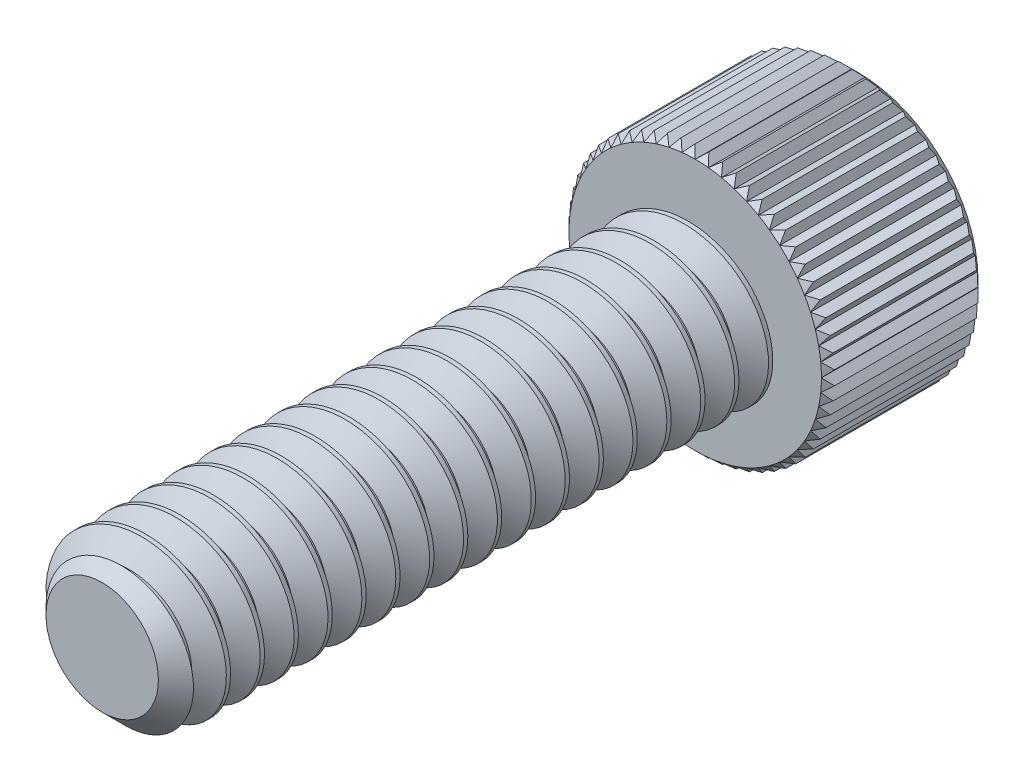
SolidWorks part; units mm, degrees
note: '?' marks a value the reader was unsure of.
ref_plane "Front Plane" through (0, 0, 0) normal (0, 0, 1) x (1, 0, 0)
ref_plane "Top Plane" through (0, 0, 0) normal (0, 1, 0) x (1, 0, 0)
ref_plane "Right Plane" through (0, 0, 0) normal (1, 0, 0) x (0, 0, -1)
sketch "Sketch0" plane through (0, 0, 0) normal (1, 0, 0) x (0, 0, -1)
  line L0 (0, 0) -> (7.9375, 0) construction
  point P2 (10.1219, 0)
  point P4 (0, 0)
  dimension "D1" = 7.9375
  dimension "D2" = 2.1844
  dimension "Min Thread" = 0
sketch "Sketch1" plane through (0, 0, 0) normal (0, 0, 1) x (1, 0, 0)
  circle A0 centre (0, 0) radius 1.0922
  dimension "OD" = 2.1844
extrude "Extrude1" add sketch "Sketch1" against normal blind 7.9375
sketch "Sketch2" plane through (0, 0, 0) normal (0, 0, 1) x (1, 0, 0)
  circle A0 centre (0, 0) radius 1.0922 construction
  circle A1 centre (0, 0) radius 1.0922
curve "Helix/Spiral1" pitch 0.4536 height 8.3911 radius 1.0922 centre (0, 0, 0) axis (0, 0, -1) start towards (0, 1, 0) parameters "pitch"=0.4536
chamfer "Chamfer3" distance 0.3402 angle 45 1 edges at (1.0922, 0, 0)
sketch "Sketch3" plane through (0, 0, 0) normal (1, 0, 0) x (0, 0, -1)
  line L0 (-0.3969, 1.0922) -> (-0.2268, 0.7976)
  line L1 (-0.2268, 0.7976) -> (-0.1701, 0.7976)
  line L2 (-0.1701, 0.7976) -> (0, 1.0922)
  line L3 (-0.3969, 1.0922) -> (0, 1.0922)
  line L4 (-0.1984, 1.0922) -> (-0.1984, 0.7976) construction
  line L5 (-0.3118, 0.9449) -> (-0.085, 0.9449) construction
  line L6 (0, 1.0922) -> (0, -1.0922) construction
  dimension "D1" = 0.0567
  dimension "D2" = 0.2268
  dimension "D3" = 60
sweep "Cut-Sweep1" cut profiles "Sketch3" path "Helix/Spiral1" align with end faces yes
sketch "Sketch5" plane through (0, 0, 0) normal (1, 0, 0) x (0, 0, -1)
  line L0 (7.9375, -0.7793) -> (7.9375, 0.8061) construction
  line L1 (7.9375, 1.0922) -> (0, 1.0922)
  line L2 (7.9375, 1.0922) -> (7.9375, 0)
  line L3 (7.9375, 0) -> (-0.3975, 0)
  line L4 (0, 0) -> (7.9375, 0) construction
  line L5 (0, 1.0922) -> (-0.3975, 0)
  line L6 (0, 0) -> (10.4775, 0) construction
  dimension "D1" = 70
  dimension "D3" = 2.54
revolve "partially thread" [suppressed] add sketch "Sketch5" angle 360 about L6
sketch "Sketch6" plane through (0, 0, -7.9375) normal (0, 0, -1) x (-1, 0, 0)
  circle A0 centre (0, 0) radius 1.778
  dimension "head dia" = 3.556
extrude "Extrude2" add sketch "Sketch6" along normal blind 2.1844
sketch "Sketch7" plane through (0, 0, -10.1219) normal (0, 0, -1) x (-1, 0, 0)
  line L1 (0, 1.1457) -> (-0.9922, 0.5728)
  line L2 (-0.9922, 0.5728) -> (-0.9922, -0.5728)
  line L3 (-0.9922, -0.5728) -> (0, -1.1457)
  line L4 (0, -1.1457) -> (0.9922, -0.5728)
  line L5 (0.9922, -0.5728) -> (0.9922, 0.5728)
  line L6 (0.9922, 0.5728) -> (0, 1.1457)
  circle A0 centre (0, 0) radius 0.9922 construction
  dimension "hex dia" = 1.9844
extrude "Cut-Extrude1" cut sketch "Sketch7" against normal blind 1.4883
sketch "Sketch8" plane through (0, 0, -10.1219) normal (0, 0, -1) x (-1, 0, 0)
  circle A0 centre (0, 0) radius 1.1457
extrude "Cut-Extrude2" cut sketch "Sketch8" against normal through all draft 45
chamfer "Chamfer1" distance 0.1778 angle 45 1 edges at (-1.778, 0, -10.1219)
chamfer "Chamfer2" distance 0.0889 angle 45 1 edges at (-1.778, 0, -7.9375)
sketch "Sketch9" plane through (0, 0, 0) normal (1, 0, 0) x (0, 0, -1)
  line L0 (0, 1.0922) -> (0, -1.0922) construction
  line L1 (1.1339, 1.0922) -> (1.1339, -1.0922) construction
  line L2 (10.1219, 1.778) -> (10.1219, -1.778) construction
  line L3 (7.9375, 1.778) -> (7.9375, -1.778) construction
  line L4 (7.9375, 1.6891) -> (7.9375, -1.6891) construction
  line L5 (10.1219, -1.6002) -> (10.1219, 1.6002) construction
  line L6 (7.9375, -1.778) -> (7.9375, 1.778) construction
  line L7 (0, 0.752) -> (0, -0.752) construction
  line L8 (-0.3969, 1.0922) -> (0, 1.0922) construction
  line L9 (1.1339, 0) -> (0, 0) construction
  dimension "D1" = 1.1339
sketch "Sketch10" plane through (0, 0, -7.9375) normal (0, 0, 1) x (1, 0, 0)
  line L0 (-0.1914, 1.8669) -> (0, 1.6891)
  line L1 (0, 1.6891) -> (0.1914, 1.8669)
  line L2 (0, 1.6891) -> (0, 1.8669) construction
  line L3 (-0.1914, 1.8669) -> (0.1914, 1.8669)
  line L4 (0, -1.9618) -> (0, 1.9618) construction
  line L5 (0, 0) -> (0.0931, 1.7756) construction
  line L6 (-0.0931, 1.7756) -> (0, 0) construction
  circle A2 centre (0, 0) radius 1.778 construction
  circle A5 centre (0, 0) radius 1.6891 construction
  dimension "D1" = 6
  dimension "D2" = 0.1778
extrude "Cut-Extrude3" cut sketch "Sketch10" against normal through all
pattern_circular "CirPattern1" count 60 over 360 about axis through (0, 0, 0) along (0, 0, 1) of "Cut-Extrude3"
ref_plane "Contact Plane 1" through (0, 0, -7.9375) normal (0, 0, 1) x (1, 0, 0)
ref_axis "Center Axis 1" through (0, 0, 0.8878) along (0, 0, -1)?
equation "\"D3@Helix/Spiral1\" = \"screw length@Extrude1\"+\"pitch@Helix/Spiral1\""
equation "\"D1@Sketch3\" = \"pitch@Helix/Spiral1\"*.125"
equation "\"D2@Sketch3\" = \"pitch@Helix/Spiral1\"*.5"
equation "\"D1@Cut-Extrude1\" = \"hex dia@Sketch7\"*.75"
equation "\"D1@Chamfer1\" = \"head dia@Sketch6\"*.05"
equation "\"D1@Sketch9\" = \"pitch@Helix/Spiral1\"*2.50"
equation "\"D1@Chamfer2\" = \"D1@Chamfer1\"/2"
equation "\"D1@Chamfer3\" = \"pitch@Helix/Spiral1\"*.750"
equation "\"D1@Sketch0\" = \"screw length@Extrude1\""
equation "\"D2@Sketch0\" = \"head depth@Extrude2\""
equation "\"D2@Sketch10\"=\"D1@Chamfer1\""
equation "\"D1@CirPattern1\"=\"D3@CirPattern1\"/\"D1@Sketch10\""
